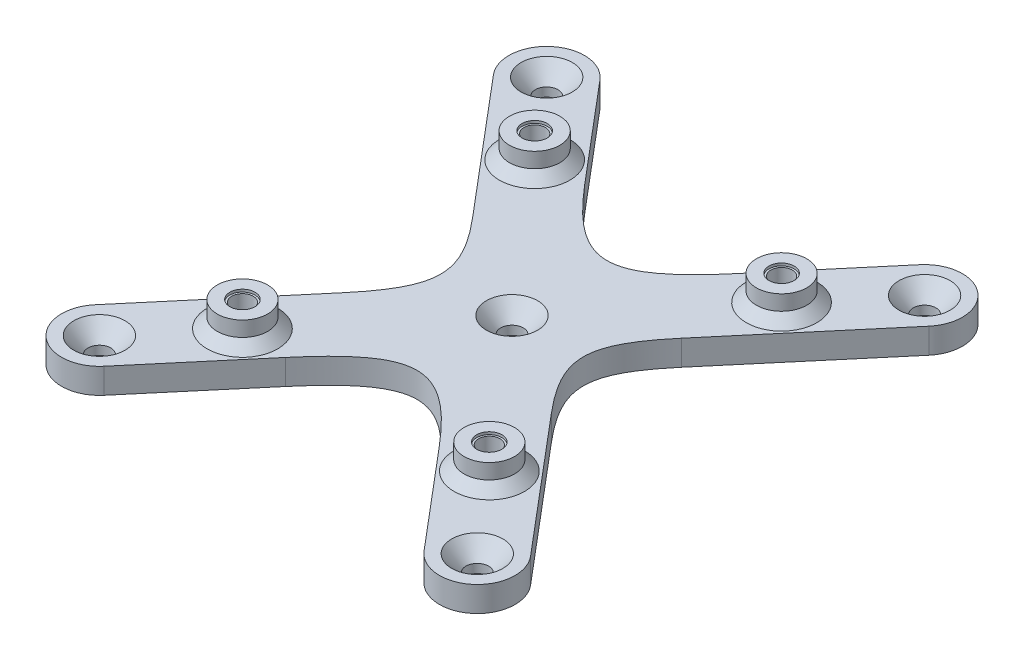
SolidWorks part; units mm, degrees
ref_plane "Front Plane" through (0, 0, 0) normal (0, 0, 1) x (1, 0, 0)
ref_plane "Top Plane" through (0, 0, 0) normal (0, 1, 0) x (1, 0, 0)
ref_plane "Right Plane" through (0, 0, 0) normal (1, 0, 0) x (0, 0, -1)
sketch "Sketch1" plane through (0, 0, 0) normal (0, 1, 0) x (1, 0, 0)
  line L0 (-37.5, 44.3878) -> (37.5, -44.3878) construction
  line L1 (-24.5, 29) -> (24.5, 29) construction
  line L2 (-24.5, 29) -> (-24.5, -29) construction
  line L3 (-24.5, -29) -> (24.5, -29) construction
  line L4 (24.5, 29) -> (24.5, -29) construction
  line L5 (-24.5, 29) -> (24.5, -29) construction
  line L6 (-24.5, -29) -> (24.5, 29) construction
  line L7 (-31.7709, 49.2279) -> (43.2291, -39.5476)
  line L8 (-43.2291, 39.5476) -> (31.7709, -49.2279)
  line L9 (-37.5, -44.3878) -> (37.5, 44.3878) construction
  line L10 (-43.2291, -39.5476) -> (31.7709, 49.2279)
  line L11 (-31.7709, -49.2279) -> (43.2291, 39.5476)
  arc A0 (-31.7709, 49.2279) -> (-43.2291, 39.5476) centre (-37.5, 44.3878) ccw
  arc A1 (31.7709, -49.2279) -> (43.2291, -39.5476) centre (37.5, -44.3878) ccw
  arc A2 (-43.2291, -39.5476) -> (-31.7709, -49.2279) centre (-37.5, -44.3878) ccw
  arc A3 (43.2291, 39.5476) -> (31.7709, 49.2279) centre (37.5, 44.3878) ccw
  point P0 (0, 0)
  point P8 (0, 0)
  point P14 (0, 0)
  dimension "D1" = 58
  dimension "D2" = 49
  dimension "D3" = 75
  dimension "D4" = 15
extrude "Boss-Extrude1" add sketch "Sketch1" along normal blind 5 contours L10 A2 L11 L8 | L8 L11 L7 L10 | L7 A0 L8 L10 | L11 A3 L10 L7 | L8 A1 L7 L11 region at (-23.1613, 0, -27.3281) region at (23.1613, 0, -27.3281) region at (0, 0, 0) region at (23.1613, 0, 27.3281) region at (-23.1613, 0, 27.3281)
sketch "Sketch2" plane through (0, 5, 0) normal (0, 1, 0) x (1, 0, 0)
  point P0 (-37.5, 44.3878)
  point P1 (37.5, 44.3878)
  point P3 (37.5, -44.3878)
  point P5 (-37.5, -44.3878)
  point P9 (0, 0)
hole_wizard "CSK for #8 Flat Head Socket Cap Screw1" positions "Sketch2" profile "Sketch3" countersink size "#8" standard "ANSI Inch" end condition through all
sketch "Sketch3" plane through (-37.5, 5, -44.3878) normal (1, 0, 0) x (0, 0, 1)
  line L0 (0, 0) -> (0, 5)
  line L1 (0, 5) -> (2.2479, 5)
  line L2 (2.2479, 5) -> (2.2479, 3.258)
  line L3 (2.2479, 3.258) -> (5.08, 0)
  line L5 (5.08, 0) -> (0, 0)
  line L6 (-2.2479, 3.258) -> (-5.08, 0) construction
  line L11 (0, -6.35) -> (0, 107.95) construction
  dimension "Thru Hole Dia." = 4.4958
  dimension "Thru Hole Depth" = 5
  dimension "Near C'Sink Dia." = 10.16
  dimension "Near C'Sink Angle" = 82
sketch "Sketch4" plane through (0, 5, 0) normal (0, 1, 0) x (1, 0, 0)
  circle A0 centre (-24.5, 29) radius 5
  circle A1 centre (24.5, 29) radius 5
  circle A2 centre (24.5, -29) radius 5
  circle A3 centre (-24.5, -29) radius 5
  dimension "D1" = 10
extrude "Boss-Extrude2" add sketch "Sketch4" along normal blind 5
chamfer "Chamfer1" distance 2 angle 45 4 edges at (-24.5, 5, 34) (24.5, 5, 34) (24.5, 5, -24) (-24.5, 5, -24)
sketch "Sketch5" plane through (0, 10, 0) normal (0, 1, 0) x (1, 0, 0)
  point P0 (-24.5, 29)
  point P1 (24.5, 29)
  point P3 (24.5, -29)
  point P5 (-24.5, -29)
hole_wizard "CBORE for M5 Hex Head Machine Screw1" positions "Sketch5" profile "Sketch6" counterbore size "M5" standard "ANSI Metric" end condition through all
sketch "Sketch6" plane through (-24.5, 10, -29) normal (1, 0, 0) x (0, 0, 1)
  line L0 (0, 0) -> (0, 10)
  line L1 (0, 10) -> (2.125, 10)
  line L3 (2.125, 10) -> (2.125, 0.5)
  line L4 (2.125, 0.5) -> (2.5, 0.5)
  line L5 (2.5, 0.5) -> (2.5, 0)
  line L7 (2.5, 0) -> (0, 0)
  line L11 (0, -6.35) -> (0, 107.95) construction
  dimension "Thru Hole Dia." = 4.25
  dimension "Thru Hole Depth" = 10
  dimension "C'Bore Dia." = 5
  dimension "C'Bore Depth" = 0.5
fillet "Fillet1" radius 20 4 edges at (-9.8182, 2.5, 0) (9.8182, 2.5, 0) (0, 2.5, 11.6216) (0, 2.5, -11.6216) conic rho 0.6
